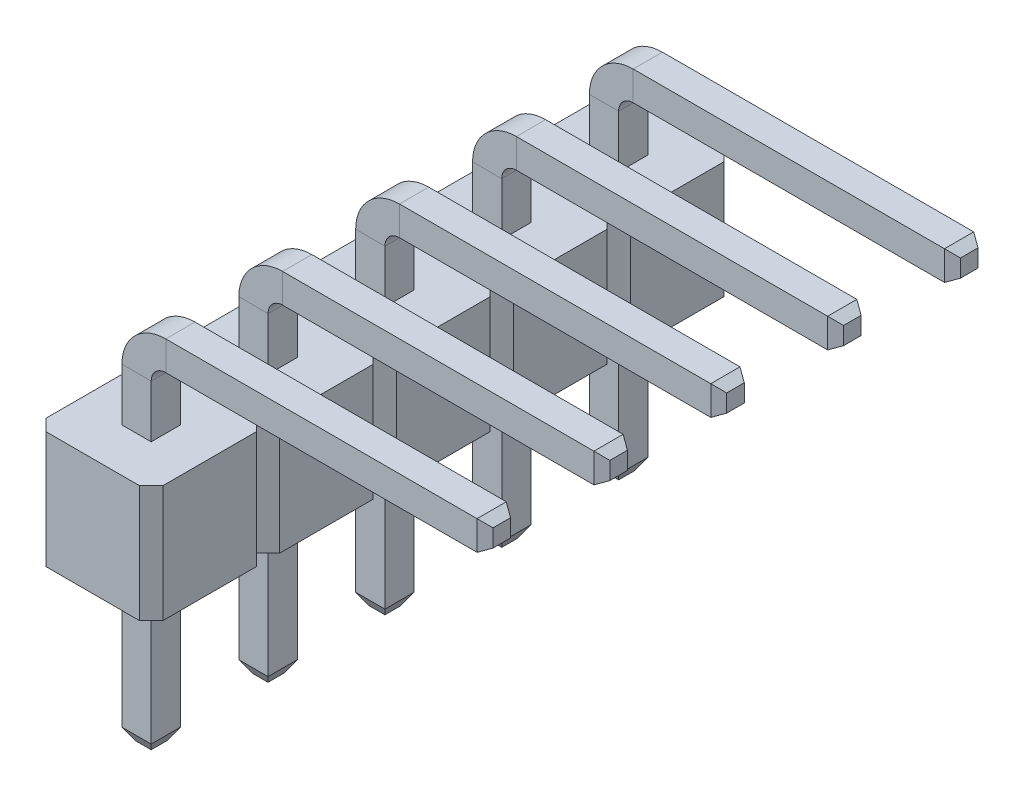
SolidWorks part; units mm, degrees
ref_plane "Front Plane" through (0, 0, 0) normal (0, 0, 1) x (1, 0, 0)
ref_plane "Top Plane" through (0, 0, 0) normal (0, 1, 0) x (1, 0, 0)
ref_plane "Right Plane" through (0, 0, 0) normal (1, 0, 0) x (0, 0, -1)
sketch "Sketch1" plane through (0, 0, 0) normal (0, 1, 0) x (1, 0, 0)
  line L0 (1.016, 1.27) -> (1.27, 1.016)
  line L1 (-1.016, -1.27) -> (1.016, -1.27)
  line L2 (-1.27, -1.016) -> (-1.27, 1.016)
  line L3 (-1.016, 1.27) -> (1.016, 1.27)
  line L4 (1.27, -1.016) -> (1.27, 1.016)
  line L5 (-1.27, -1.27) -> (1.27, 1.27) construction
  line L6 (-1.27, 1.27) -> (1.27, -1.27) construction
  line L7 (1.016, -1.27) -> (1.27, -1.016)
  line L8 (-1.27, -1.016) -> (-1.016, -1.27)
  line L9 (-1.27, 1.016) -> (-1.016, 1.27)
  point P0 (0, 0)
  dimension "D1" = 2.54
  dimension "D2" = 2.54
extrude "Boss-Extrude1" add sketch "Sketch1" along normal blind 2.54
sketch "Sketch2" plane through (0, 0, 0) normal (0, 0, 1) x (1, 0, 0)
  line L0 (0, 0) -> (0, -3.4036)
  line L1 (0, 0) -> (0, 3.683)
  line L2 (0.635, 4.318) -> (7.62, 4.318)
  line L3 (-1.016, 2.54) -> (1.016, 2.54) construction
  arc A0 (0, 3.683) -> (0.635, 4.318) centre (0.635, 3.683) cw
  point P9 (0, 4.318)
  dimension "D4" = 0.635
  dimension "D1" = 1.778
  dimension "D2" = 7.62
  dimension "D3" = 3.4036
ref_plane "Plane1" through (0, -3.4036, 0) normal (0, -1, 0) x (-1, 0, 0)
sketch "Sketch3" plane through (0, -3.4036, 0) normal (0, -1, 0) x (-1, 0, 0)
  line L1 (0.3175, 0.3175) -> (-0.3175, 0.3175)
  line L2 (0.3175, 0.3175) -> (0.3175, -0.3175)
  line L3 (0.3175, -0.3175) -> (-0.3175, -0.3175)
  line L4 (-0.3175, 0.3175) -> (-0.3175, -0.3175)
  line L5 (0.3175, 0.3175) -> (-0.3175, -0.3175) construction
  line L6 (0.3175, -0.3175) -> (-0.3175, 0.3175) construction
  point P0 (0, 0)
  dimension "D1" = 0.635
  dimension "D2" = 0.635
sweep "Sweep1" add profiles "Sketch3" path "Sketch2"
chamfer "Chamfer1" distance 0.254 angle 30 4 edges at (0, -3.4036, -0.3175) (-0.3175, -3.4036, 0) (0, -3.4036, 0.3175) (0.3175, -3.4036, 0) first distance on face at (0, -1.7018, -0.3175) first distance on face at (-0.3175, -1.7018, 0) first distance on face at (0, -1.7018, 0.3175) first distance on face at (0.3175, -1.7018, 0)
chamfer "Chamfer2" distance 0.127 angle 60 4 edges at (7.62, 4.318, 0.3175) (7.62, 4.6355, 0) (7.62, 4.318, -0.3175) (7.62, 4.0005, 0) first distance on face at (7.62, 4.318, 0)
pattern_linear "LPattern1" count 5 spacing 2.54 along (0, 0, 1) of "Boss-Extrude1", "Chamfer1", "Chamfer2", "Sweep1"
ref_plane "Plane2" through (0, 0, 5.08) normal (0, 0, 1) x (1, 0, 0)
